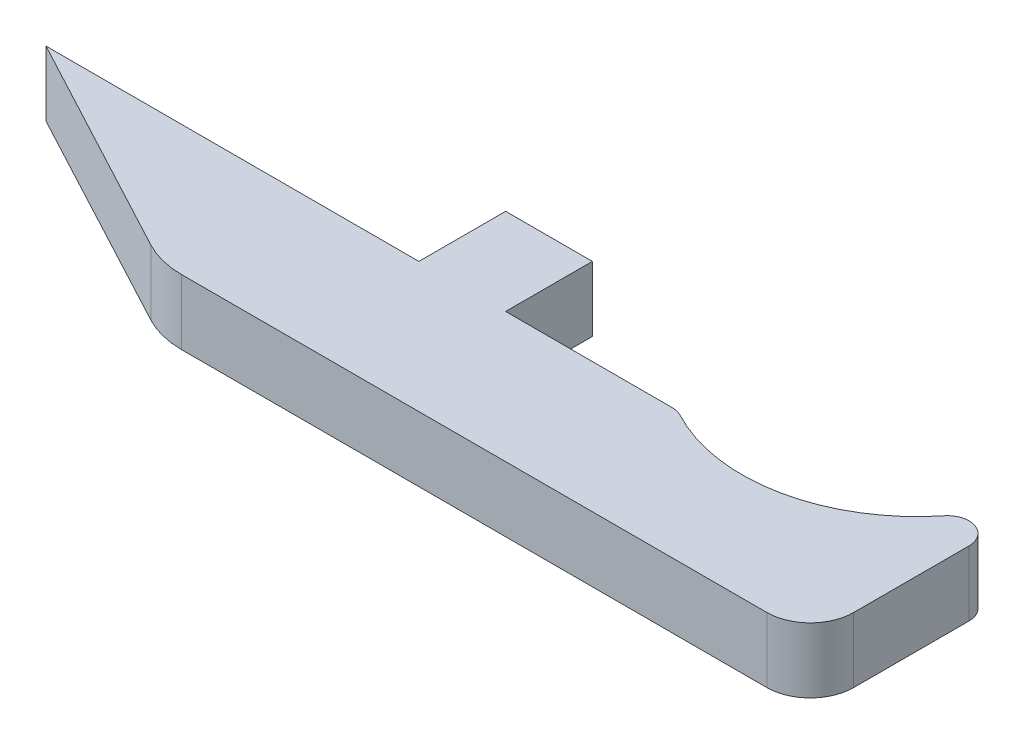
SolidWorks part; units mm, degrees
material "AISI 4130 Steel, annealed at 865C"
ref_plane "X-Y Datum" through (0, 0, 0) normal (0, 0, 1) x (1, 0, 0)
ref_plane "X-Z Datum" through (0, 0, 0) normal (0, 1, 0) x (1, 0, 0)
ref_plane "Y-Z Datum" through (0, 0, 0) normal (1, 0, 0) x (0, 0, -1)
sketch "Sketch1" plane through (0, 0, 0) normal (0, 1, 0) x (1, 0, 0)
  line L0 (58.9432, -34.753) -> (58.9432, -34.7341) construction
  line L1 (58.9432, -45.8687) -> (3.2156, -45.8687)
  line L2 (58.9432, -45.8687) -> (58.9432, -34.7435)
  line L3 (24.1452, -55.3937) -> (71.7702, -55.3937)
  line L4 (71.7702, -34.7435) -> (71.7702, -55.3937)
  line L5 (6.2845, -45.8687) -> (24.1452, -55.3937)
  line L8 (33.5895, -45.8687) -> (3.1095, -45.8687) construction
  line L9 (33.5895, -45.8687) -> (3.1095, -45.8687)
  circle A0 centre (58.9432, -34.7435) radius 12.827
  circle A1 centre (58.9432, -34.7435) radius 12.7
  circle A2 centre (58.9432, -34.7435) radius 12.7 construction
  dimension "D3" = 25.654
  dimension "D5" = 9.525
  dimension "D1" = 55.7276
  dimension "D2" = 11.1252
  dimension "D4" = 3.175
  dimension "D6" = 47.625
extrude "Boss-Extrude1" add sketch "Sketch1" along normal blind 4.7625 contours L1 A0 region at (43.8554, 0, 50.211)
fillet "Fillet1" radius 1.5875 2 edges at (52.5587, 2.3813, 45.8687) (71.7702, 2.3813, 34.7435)
fillet "Fillet2" radius 6.35 1 edges at (24.1452, 2.3813, 55.3937)
fillet "Fillet3" radius 3.175 1 edges at (71.7702, 2.3813, 55.3937)
sketch "Sketch2" plane through (0, 0, 45.8687) normal (0, 0, -1) x (-1, 0, 0)
  line L0 (-52.1488, 4.7625) -> (-6.2845, 4.7625) construction
  line L1 (-39.9395, 4.7625) -> (-33.5895, 4.7625)
  line L2 (-39.9395, 4.7625) -> (-39.9395, 0)
  line L3 (-39.9395, 0) -> (-33.5895, 0)
  line L4 (-33.5895, 4.7625) -> (-33.5895, 0)
  line L5 (-52.1488, 0) -> (-6.2845, 0) construction
  line L6 (-6.2845, 4.7625) -> (-6.2845, 0) construction
  dimension "D1" = 27.305
  dimension "D2" = 6.35
extrude "Boss-Extrude2" add sketch "Sketch2" along normal blind 6.35
fillet "Fillet4" [suppressed] radius 0.7937
